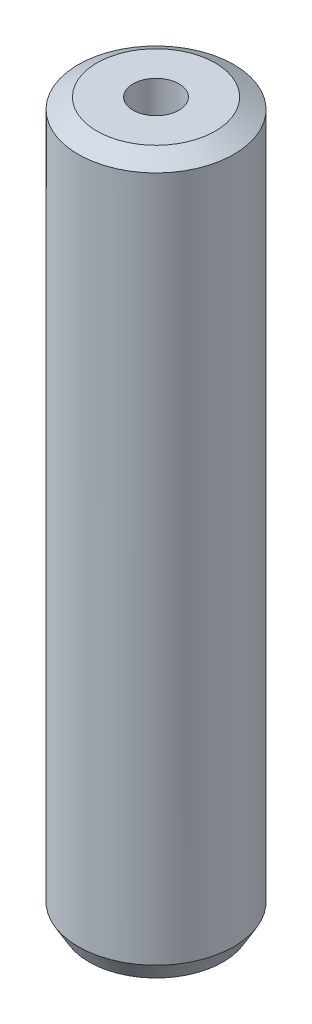
SolidWorks part; units mm, degrees
ref_plane "Front Plane" through (0, 0, 0) normal (0, 0, 1) x (1, 0, 0)
ref_plane "Top Plane" through (0, 0, 0) normal (0, 1, 0) x (1, 0, 0)
ref_plane "Right Plane" through (0, 0, 0) normal (1, 0, 0) x (0, 0, -1)
sketch "Sketch1" plane through (0, 0, 0) normal (0, 1, 0) x (1, 0, 0)
  circle A0 centre (0, 0) radius 35
  dimension "SHAFT_OD" = 70
extrude "Boss-Extrude1" add sketch "Sketch1" along normal blind 321.8702
sketch "Sketch2" plane through (0, 0, 0) normal (0, 1, 0) x (1, 0, 0)
  circle A0 centre (0, 0) radius 10.313
  dimension "BORE_D" = 20.6259
extrude "Cut-Extrude1" cut sketch "Sketch2" along normal through all
chamfer "Chamfer1" distance 4.8477 angle 60 2 edges at (0, 321.8702, 35) (0, 0, 35) first distance on face at (0, 321.8702, 35) first distance on face at (0, 0, 10.313)
